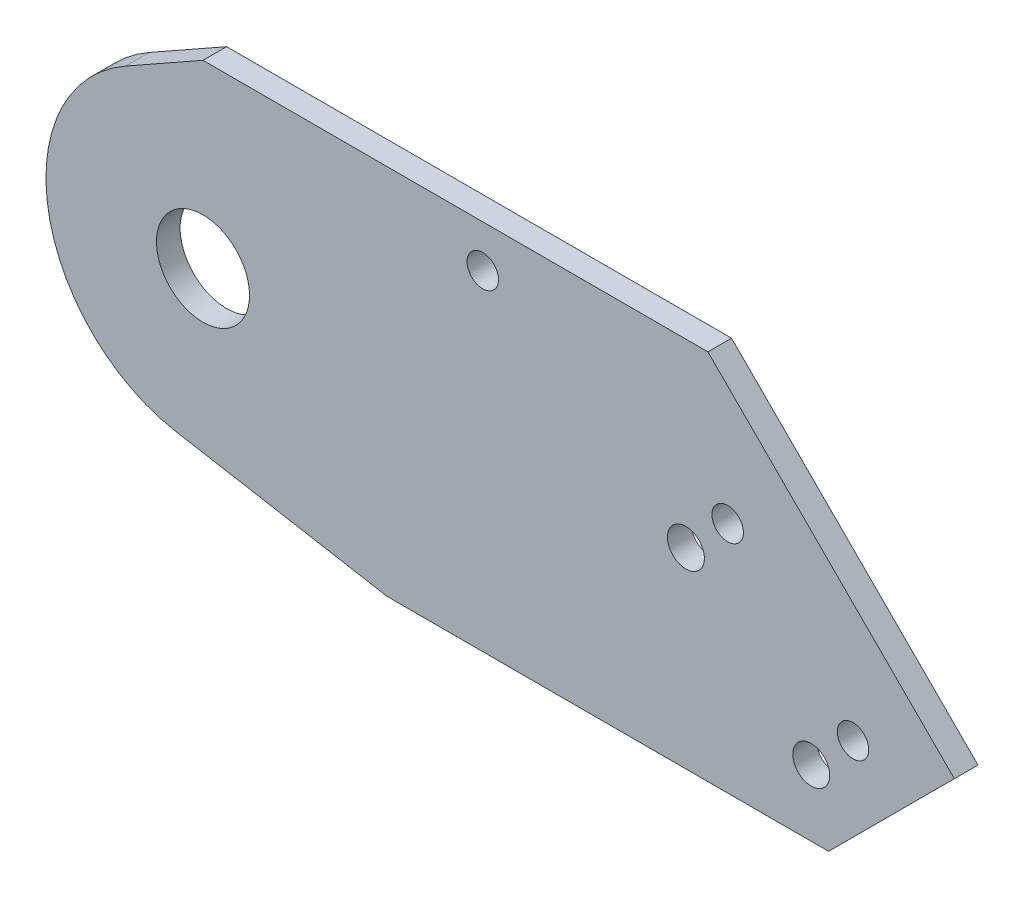
SolidWorks part; units mm, degrees
note: '?' marks a value the reader was unsure of.
ref_plane "Front" through (0, 0, 0) normal (0, 0, 1) x (1, 0, 0)
ref_plane "Top" through (0, 0, 0) normal (0, 1, 0) x (1, 0, 0)
ref_plane "Right" through (0, 0, 0) normal (1, 0, 0) x (0, 0, -1)
ref_axis "side-side" through (80.9, 0, 0) along (-1, 0, 0)?
ref_axis "up-down" through (0, 50, 0) along (0, -1, 0)?
ref_axis "front-back" through (0, 0, -80.9) along (0, 0, 1)?
sketch "Sketch1" plane through (0, 0, 0) normal (0, 0, 1) x (1, 0, 0)
  line L2 (46.0949, 11.7338) -> (34.7797, 0.4187)
  line L3 (34.7797, 0.4187) -> (52.7402, -17.5418)
  line L10 (65.9023, -6.996) -> (45.3962, 13.5101)
  line L11 (45.3962, 13.5101) -> (45.3862, 13.5)
  line L12 (-2.3443, -13.2949) -> (15.8327, -16.5)
  line L13 (15.8327, -16.5) -> (52.2562, -16.5)
  line L14 (59.3273, -13.5711) -> (65.9023, -6.996)
  line L15 (64.0554, -6.2267) -> (52.7402, -17.5418)
  circle A1 centre (0, 0) radius 4
  arc A6 (45.3862, 13.5) -> (-2.4238, 13.2806) centre (22.0982, -121.0825) ccw
  arc A7 (-2.4238, 13.2806) -> (-2.3443, -13.2949) centre (0, 0) ccw
  arc A8 (52.2562, -16.5) -> (59.3273, -13.5711) centre (52.2562, -6.5) ccw
  circle A9 centre (24.0532, 11.8676) radius 1.3526
  circle A12 centre (45.107, 3.5618) radius 1.3525
  circle A13 centre (55.8833, -7.2145) radius 1.3525
sketch "Sketch2" plane through (0, 0, 0) normal (0, 0, 1) x (1, 0, 0)
  line L0 (65.9023, -6.996) -> (45.3962, 13.5101) construction
  line L2 (15.8327, -16.5) -> (52.2562, -16.5) construction
  line L3 (64.5942, -5.6879) -> (43.4063, 15.5)
  line L5 (15.8327, -16.5) -> (53.7821, -16.5)
  line L6 (0, 15.5) -> (43.4063, 15.5)
  line L7 (-6.6331, 11.7581) -> (0, 15.5)
  line L8 (-2.3443, -13.2949) -> (15.8327, -16.5) construction
  line L9 (-2.3443, -13.2949) -> (15.8327, -16.5)
  line L10 (64.0554, -6.2267) -> (52.7402, -17.5418) construction
  line L11 (64.5942, -5.6879) -> (53.7821, -16.5)
  arc A0 (45.3862, 13.5) -> (-2.4238, 13.2806) centre (22.0982, -121.0825) ccw construction
  arc A1 (-2.4238, 13.2806) -> (-2.3443, -13.2949) centre (0, 0) ccw construction
  arc A2 (-6.6331, 11.7581) -> (-2.3443, -13.2949) centre (0, 0) ccw
  circle A3 centre (0, 0) radius 4 construction
  circle A4 centre (24.0532, 11.8676) radius 1.3526 construction
  circle A5 centre (0, 0) radius 4
  circle A6 centre (24.0532, 11.8676) radius 1.3526
  dimension "D1" = 8
  dimension "D2" = 2.7051
extrude "Boss-Extrude1" add sketch "Sketch2" along normal blind 2.032
hole_wizard "#6 Clearance Hole1" [suppressed] positions "Sketch4" profile "Sketch3" hole size "#6" standard "ANSI Inch"
sketch "Sketch4" plane through (0, 0, 0) normal (0, 0, -1) x (-1, 0, 0)
  point P0 (-45.107, 3.5618)
  point P3 (-55.8833, -7.2145)
sketch "Sketch3" plane through (45.107, 3.5618, 0) normal (1, 0, 0) x (0, 1, 0)
  line L0 (0, 0) -> (0, 2.032)
  line L1 (0, 2.032) -> (1.8986, 2.032)
  line L2 (1.8986, 2.032) -> (1.8986, 0)
  line L5 (1.8986, 0) -> (0, 0)
  line L11 (0, -6.35) -> (0, 107.95) construction
  dimension "Thru Hole Dia." = 3.7973
  dimension "Thru Hole Depth" = 2.032
sketch "Sketch5" plane through (0, 0, 0) normal (0, 0, -1) x (-1, 0, 0)
  circle A0 centre (-41.5149, -0.0303) radius 1.5875 construction
  circle A1 centre (-52.2912, -10.8066) radius 1.5875 construction
  circle A2 centre (-41.5149, -0.0303) radius 1.5875
  circle A3 centre (-52.2912, -10.8066) radius 1.5875
  circle A4 centre (-45.107, 3.5618) radius 1.3525 construction
  circle A5 centre (-55.8833, -7.2145) radius 1.3525 construction
  circle A6 centre (-45.107, 3.5618) radius 1.3525
  circle A7 centre (-55.8833, -7.2145) radius 1.3525
extrude "Cut-Extrude1" cut sketch "Sketch5" against normal through all
